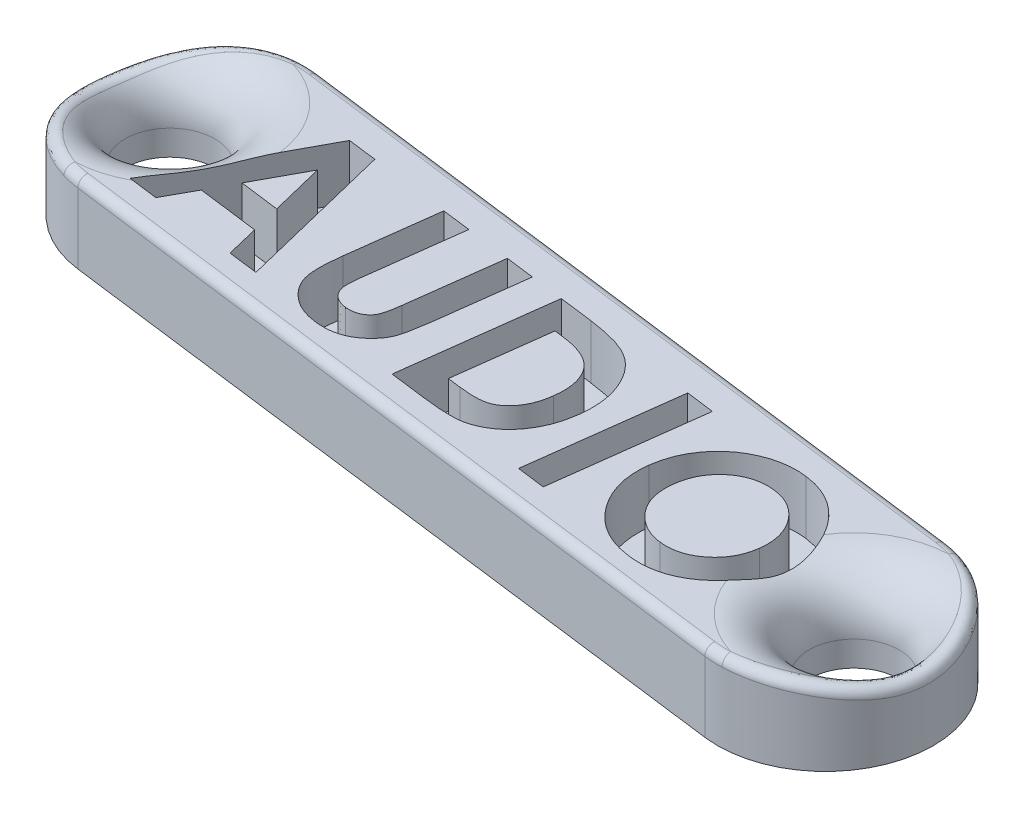
SolidWorks part; units mm, degrees
ref_plane "Front Plane" through (0, 0, 0) normal (0, 0, 1) x (1, 0, 0)
ref_plane "Top Plane" through (0, 0, 0) normal (0, 1, 0) x (1, 0, 0)
ref_plane "Right Plane" through (0, 0, 0) normal (1, 0, 0) x (0, 0, -1)
sketch "Sketch1" plane through (0, 0, 0) normal (0, 1, 0) x (1, 0, 0)
  line L0 (-10, 1.2802) -> (10, -1.2802) construction
  line L1 (-9.6191, 4.2559) -> (10.3809, 1.6955)
  line L2 (-10.3809, -1.6955) -> (9.6191, -4.2559)
  arc A0 (-9.6191, 4.2559) -> (-10.3809, -1.6955) centre (-10, 1.2802) ccw
  arc A1 (9.6191, -4.2559) -> (10.3809, 1.6955) centre (10, -1.2802) ccw
  point P2 (0, 0)
  dimension "D1" = 6
  dimension "D2" = 20
extrude "Boss-Extrude1" add sketch "Sketch1" along normal blind 2.2
sketch "Sketch2" plane through (0, 2.2, 0) normal (0, 1, 0) x (1, 0, 0)
  line L0 (-12.3025, -0.643) -> (11.7437, -3.7214) construction
  line L1 (-10.3809, -1.6955) -> (9.6191, -4.2559) construction
  arc A0 (-9.6191, 4.2559) -> (-10.3809, -1.6955) centre (-10, 1.2802) ccw construction
  arc A1 (9.6191, -4.2559) -> (10.3809, 1.6955) centre (10, -1.2802) ccw construction
  text T0 "<b>AUDIO</b>" font "Century Gothic" height in points 16
  dimension "D1" = 0
  dimension "D2" = 0.8
sketch "Sketch3" plane through (0, 2.2, 0) normal (0, 1, 0) x (1, 0, 0)
  line L0 (-10.3809, -1.6955) -> (9.6191, -4.2559) construction
  circle A0 centre (-10.911, 1.3968) radius 1.25
  circle A1 centre (10.911, -1.3968) radius 1.25
  dimension "D1" = 2.5
  dimension "D2" = 2.5
  dimension "D3" = 3
  dimension "D4" = 3
  dimension "D5" = 11
  dimension "D6" = 11
extrude "Cut-Extrude1" cut sketch "Sketch3" against normal blind 3
extrude "Cut-Extrude2" cut sketch "Sketch2" against normal blind 1.5
fillet "Fillet1" radius 1.5 2 edges at (10.911, 2.2, 2.6468) (-10.911, 2.2, -0.1468)
fillet "Fillet7" radius 0.25 8 edges at (11.0025, 2.2, -1.5474) (12.9997, 2.0493, 1.2384) (10.2579, 2.2, 4.2691) (-11.0025, 2.2, 1.5474) (-12.9997, 2.0493, -1.2384) (-10.2579, 2.2, -4.2691) (-0.3809, 2.2, 2.9757) (0.3809, 2.2, -2.9757)
